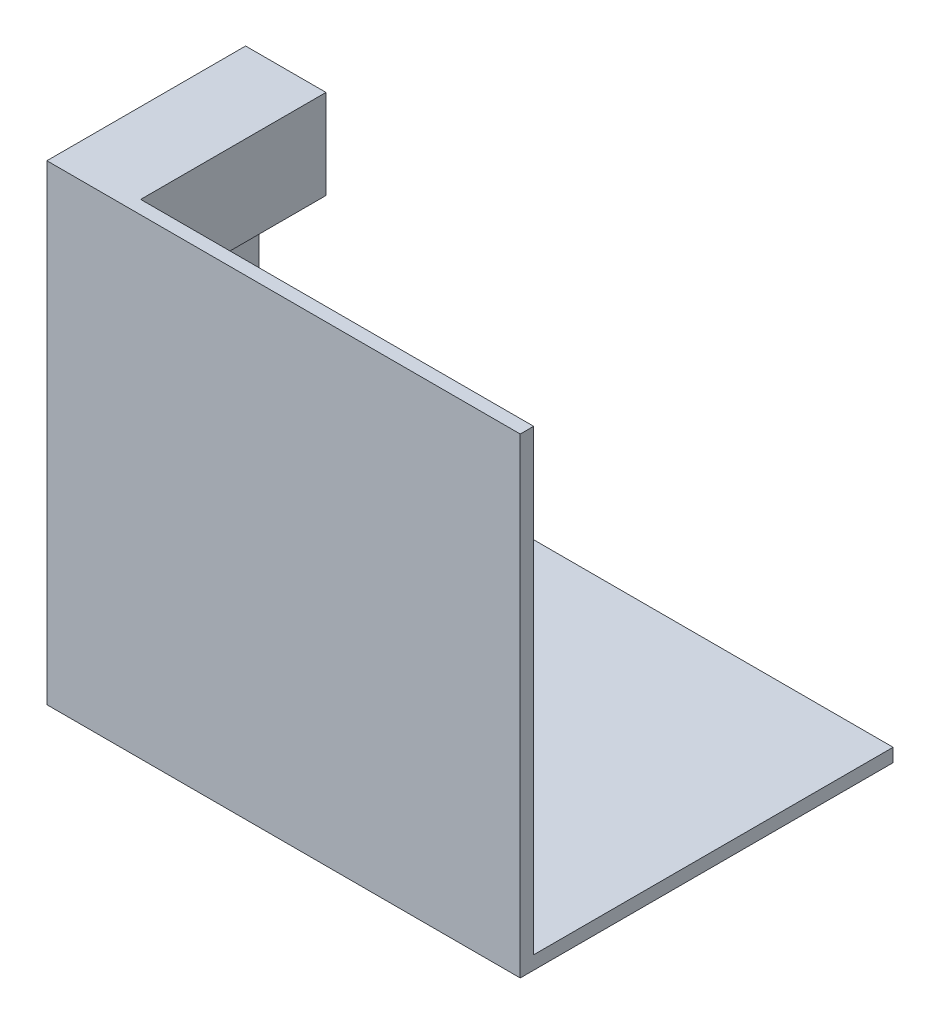
SolidWorks part; units mm, degrees
ref_plane "Front Plane" through (0, 0, 0) normal (0, 0, 1) x (1, 0, 0)
ref_plane "Top Plane" through (0, 0, 0) normal (0, 1, 0) x (1, 0, 0)
ref_plane "Right Plane" through (0, 0, 0) normal (1, 0, 0) x (0, 0, -1)
sketch "Sketch1" plane through (0, 0, 0) normal (0, 1, 0) x (1, 0, 0)
  line L1 (-50, -38.75) -> (50, -38.75)
  line L2 (-50, -38.75) -> (-50, 38.75)
  line L3 (-50, 38.75) -> (50, 38.75)
  line L4 (50, -38.75) -> (50, 38.75)
  line L5 (-50, -38.75) -> (50, 38.75) construction
  line L6 (-50, 38.75) -> (50, -38.75) construction
  point P0 (0, 0)
  dimension "D1" = 77.5
  dimension "D2" = 100
extrude "Boss-Extrude1" add sketch "Sketch1" along normal blind 3 contours L3 L4 L1 L2
sketch "Sketch2" plane through (0, 3, 0) normal (0, 1, 0) x (1, 0, 0)
  line L4 (-50, -38.75) -> (50, -38.75) construction
  line L5 (50, -38.75) -> (50, 38.75) construction
  line L6 (-50, 38.75) -> (50, 38.75) construction
  line L7 (-50, -38.75) -> (-50, 38.75) construction
  line L8 (-53, 41.75) -> (-53, -41.75)
  line L9 (-53, -41.75) -> (53, -41.75)
  line L10 (53, -41.75) -> (53, 41.75)
  line L11 (53, 41.75) -> (-53, 41.75)
  line L12 (-53, 41.75) -> (-53, -41.75)
  line L13 (-53, -41.75) -> (53, -41.75)
  line L14 (53, -41.75) -> (53, 41.75)
  line L15 (53, 41.75) -> (-53, 41.75)
  line L16 (-50, -38.75) -> (50, -38.75)
  line L17 (50, -38.75) -> (50, 38.75)
  line L18 (-50, 38.75) -> (50, 38.75)
  line L19 (-50, -38.75) -> (-50, 38.75)
  dimension "D1" = 3
extrude "Boss-Extrude2" add sketch "Sketch2" along normal blind 102.5 and the other way blind 3
sketch "Sketch3" plane through (0, 0, -41.75) normal (0, 0, -1) x (-1, 0, 0)
  line L1 (-53, 105.5) -> (53, 105.5)
  line L2 (-53, 105.5) -> (-53, 3)
  line L3 (-53, 3) -> (53, 3)
  line L4 (53, 105.5) -> (53, 3)
  line L5 (-53, 105.5) -> (53, 105.5) construction
  line L7 (-53, 0) -> (53, 0) construction
  line L9 (-53, 0) -> (-53, 105.5) construction
  point P6 (0, 105.5)
  dimension "D1" = 3
extrude "Cut-Extrude1" cut sketch "Sketch3" against normal blind 39
sketch "Sketch4" plane through (53, 0, 0) normal (1, 0, 0) x (0, 0, -1)
  line L0 (-41.75, 105.5) -> (2.75, 105.5) construction
  line L1 (-38.75, 105.5) -> (2.75, 105.5)
  line L2 (-38.75, 105.5) -> (-38.75, 3)
  line L3 (-38.75, 3) -> (2.75, 3)
  line L4 (2.75, 105.5) -> (2.75, 3)
  line L5 (-41.75, 0) -> (-41.75, 105.5) construction
  dimension "D1" = 3
extrude "Cut-Extrude2" cut sketch "Sketch4" against normal up to next
sketch "Sketch5" plane through (-50, 0, 0) normal (1, 0, 0) x (0, 0, -1)
  line L0 (2.75, 105.5) -> (2.75, 3) construction
  line L1 (-38.75, 105.5) -> (2.75, 105.5)
  line L2 (-38.75, 105.5) -> (-38.75, 85.5)
  line L3 (-38.75, 85.5) -> (2.75, 85.5)
  line L4 (2.75, 105.5) -> (2.75, 85.5)
  dimension "D1" = 20
extrude "Boss-Extrude3" add sketch "Sketch5" along normal blind 15
